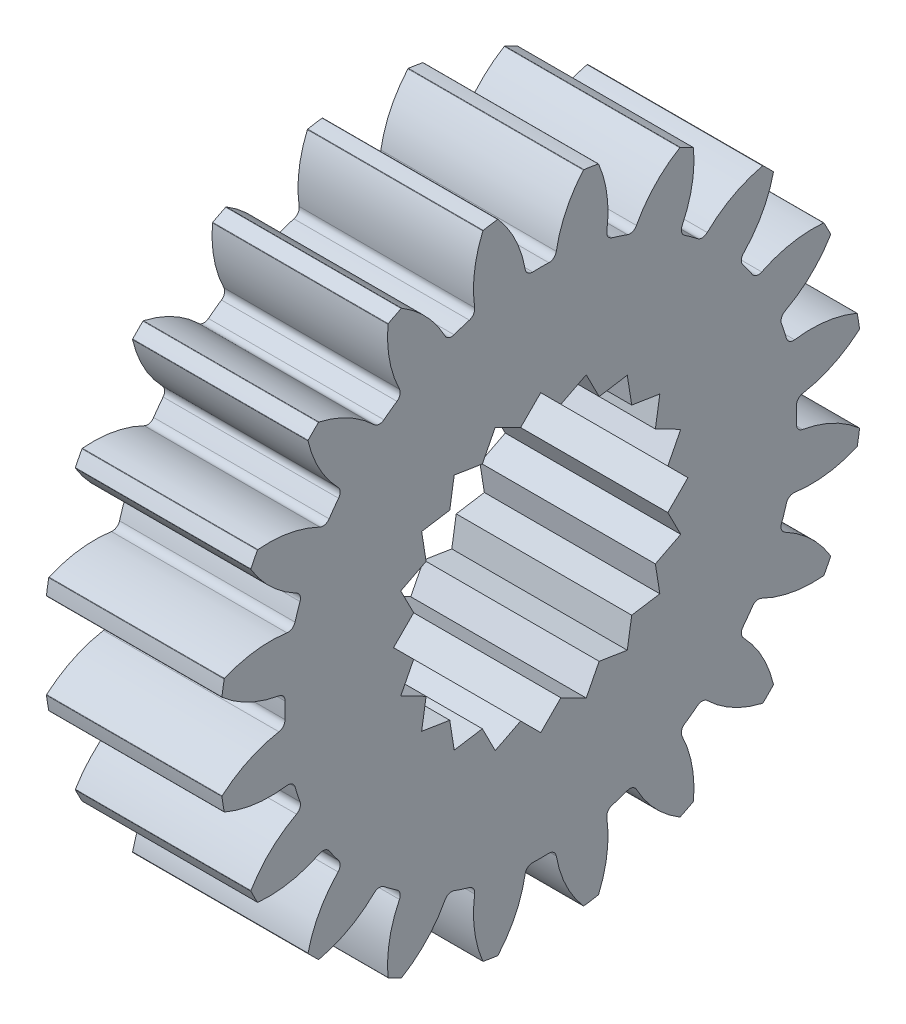
SolidWorks part; units mm, degrees
ref_plane "Plane1" through (0, 0, 0) normal (0, 0, 1) x (1, 0, 0)
ref_plane "Plane2" through (0, 0, 0) normal (0, 1, 0) x (1, 0, 0)
ref_plane "Plane3" through (0, 0, 0) normal (1, 0, 0) x (0, 0, -1)
sketch "HoldingSke" plane through (0, 0, 0) normal (0, 1, 0) x (1, 0, 0)
  line L0 (0, 0) -> (1.8794, -0.684)
  line L1 (-15, 0) -> (100, 0) construction
  line L2 (0, 0) -> (-2.1039, 2.3779)
  line L3 (0, 0) -> (-11.863, 4.5341)
  line L4 (0, 0) -> (8.1152, 2.9537)
  line L5 (0, 0) -> (-46.8476, -17.4728)
  line L6 (0, 0) -> (-2.4869, -1.6779)
  line L7 (-2.1039, 2.3779) -> (8.6586, 51.2059)
  line L8 (-76.2, 54.61) -> (-75.9, 54.61)
  line L9 (-71.009, 38.7566) -> (-53.1078, 45.2721)
  line L10 (-76.2, 71.12) -> (104.1128, 71.12)
  line L11 (0, 0) -> (-3, 0)
  line L12 (-76.2, 101.6) -> (-76.181, 101.6)
  line L13 (24.9733, 27.94) -> (52.9518, 28.4284)
  line L14 (24.9733, 27.94) -> (24.9743, 27.94)
  line L15 (24.9733, 27.94) -> (100.4006, 29.5858)
  line L16 (-63.627, -0.5) -> (-12.827, -0.5)
  circle A0 centre (0, 0) radius 1
  circle A1 centre (0, 0) radius 4.374
  circle A2 centre (0, 0) radius 37.5
  circle A3 centre (0, 0) radius 1
  dimension "MHD" = 8.748
  dimension "Hub_dia" = 75
  dimension "Bore" = 2
  dimension "MBD" = 2
  dimension "Num_teeth" = 20
  dimension "Pitch" = 2
  dimension "Overall_len" = 50
  dimension "Show_teeth" = 20
  dimension "Thickness" = 3
  dimension "OAL" = 50.0001
  dimension "T_dim" = 0.3
  dimension "Ap" = 20
  dimension "H" = 19.05
  dimension "Pitch_radius" = 180.3128
  dimension "Width" = 3
  dimension "Backlash" = 0.019
  dimension "Addendum_fac" = 1
  dimension "Dedendum_fac" = 1.25
  dimension "Clearance_fac" = 0.25
  dimension "Dedendum_add" = 0.001
  dimension "Module" = 0.5
sketch "BasProSke" plane through (0, 0, 0) normal (0, 1, 0) x (1, 0, 0)
  line L0 (-10, 0) -> (60, 0) construction
  line L1 (0, 0) -> (0, 5.5)
  line L2 (0, 0) -> (3, 0)
  line L3 (3, 0) -> (3, 5.5)
  line L4 (3, 5.5) -> (0, 5.5)
  dimension "Thickness" = 3
  dimension "Diameter" = 11
revolve "Base-Revolve" add sketch "BasProSke" angle 360 about L0
sketch "TooCutSke" plane through (0, 0, 0) normal (1, 0, 0) x (0, 0, -1)
  line L1 (0, 0) -> (0, 107) construction
  line L2 (0, 0) -> (-0.4255, 4.9819) construction
  line L3 (0, 0) -> (-1.5603, 9.8514) construction
  line L4 (-0.4255, 4.9819) -> (-0.7802, 4.9257) construction
  arc A0 (0.2499, 4.3669) -> (-0.2499, 4.3669) centre (0, 0) ccw
  arc A1 (0.7528, 5.4739) -> (-0.7528, 5.4739) centre (0, 0) ccw
  circle A2 centre (0, 0) radius 5 construction
  circle A3 centre (0, 0) radius 4.6985 construction
  arc A4 (-0.2499, 4.3669) -> (-0.7528, 5.4739) centre (-2.2361, 4.1322) ccw
  arc A5 (0.7528, 5.4739) -> (0.2499, 4.3669) centre (2.2361, 4.1322) ccw
  dimension "Root_dia" = 8.748
  dimension "Overcut_dia" = 11.0508
  dimension "Pitch_dia" = 10
  dimension "Base_dia" = 9.3969
  dimension "Flank_rad" = 2
  dimension "Half_ang" = 9
  dimension "Half_CT" = 0.359
extrude "ToothCut" cut sketch "TooCutSke" along normal through all
fillet "Breaks" radius 0.01 2 edges at (1.5, 5.451, -0.7325) (1.5, 5.451, 0.7325) tangent propagation no
fillet "RootFillets" radius 0.126 2 edges at (1.5, 4.3669, -0.2499) (1.5, 4.3669, 0.2499)
pattern_circular "TeethCuts" count 20 every 18 about axis through (-10, 0, 0) along (1, 0, 0) of "ToothCut", "RootFillets", "Breaks"
sketch "HubNeaOneSke" plane through (0, 0, 0) normal (-1, 0, 0) x (0, 0, 1)
  circle A0 centre (0, 0) radius 4.374
  dimension "Diameter" = 8.748
extrude "HubNearOne" [suppressed] add sketch "HubNeaOneSke" along normal blind 47.0001
sketch "HubNeaBotSke" plane through (0, 0, 0) normal (-1, 0, 0) x (0, 0, 1)
  circle A0 centre (0, 0) radius 4.374
  dimension "Diameter" = 8.748
extrude "HubNearBoth" [suppressed] add sketch "HubNeaBotSke" along normal blind 23.5
ref_plane "FarPln" through (3, 0, 0) normal (1, 0, 0) x (0, 0, -1)
sketch "HubFarSke" plane through (3, 0, 0) normal (1, 0, 0) x (0, 0, -1)
  circle A0 centre (0, 0) radius 4.374
  dimension "Diameter" = 8.748
extrude "HubFar" [suppressed] add sketch "HubFarSke" along normal blind 23.5
sketch "BorSke" plane through (0, 0, 0) normal (1, 0, 0) x (0, 0, -1)
  circle A0 centre (0, 0) radius 1
  dimension "Diameter" = 2
extrude "Bore" cut sketch "BorSke" along normal mid plane 100.0001
sketch "KeySke" plane through (0, 0, 0) normal (1, 0, 0) x (0, 0, -1)
  line L0 (-0.4, 0) -> (-0.4, 1.3)
  line L1 (-0.4, 1.3) -> (0.4, 1.3)
  line L2 (0.4, 1.3) -> (0.4, 0)
  line L3 (0, 0) -> (0, 34) construction
  line L4 (-0.4, 0) -> (0.4, 0)
  dimension "Offset" = 1.3
  dimension "Width" = 0.8
extrude "Keyway" [suppressed] cut sketch "KeySke" along normal mid plane 100.0001
pattern_circular "Keyway2" [suppressed] count 2 every 90 about axis through (-10, 0, 0) along (1, 0, 0)
sketch "Sketch1" plane through (0, 0, 0) normal (-1, 0, 0) x (0, 0, 1)
  line L0 (0, 2.0758) -> (0, 2.375) construction
  line L1 (-0.3247, 2.0503) -> (0, 2.375)
  line L2 (0, 2.375) -> (0.3247, 2.0503)
  line L3 (0.7339, 2.2588) -> (0.9424, 1.8496)
  line L4 (0.3247, 2.0503) -> (0.7339, 2.2588)
  line L5 (1.396, 1.9214) -> (1.4678, 1.4678)
  line L6 (0.9424, 1.8496) -> (1.396, 1.9214)
  line L7 (1.9214, 1.396) -> (1.8496, 0.9424)
  line L8 (1.4678, 1.4678) -> (1.9214, 1.396)
  line L9 (2.2588, 0.7339) -> (2.0503, 0.3247)
  line L10 (1.8496, 0.9424) -> (2.2588, 0.7339)
  line L11 (2.375, 0) -> (2.0503, -0.3247)
  line L12 (2.0503, 0.3247) -> (2.375, 0)
  line L13 (2.2588, -0.7339) -> (1.8496, -0.9424)
  line L14 (2.0503, -0.3247) -> (2.2588, -0.7339)
  line L15 (1.9214, -1.396) -> (1.4678, -1.4678)
  line L16 (1.8496, -0.9424) -> (1.9214, -1.396)
  line L17 (1.396, -1.9214) -> (0.9424, -1.8496)
  line L18 (1.4678, -1.4678) -> (1.396, -1.9214)
  line L19 (0.7339, -2.2588) -> (0.3247, -2.0503)
  line L20 (0.9424, -1.8496) -> (0.7339, -2.2588)
  line L21 (0, -2.375) -> (-0.3247, -2.0503)
  line L22 (0.3247, -2.0503) -> (0, -2.375)
  line L23 (-0.7339, -2.2588) -> (-0.9424, -1.8496)
  line L24 (-0.3247, -2.0503) -> (-0.7339, -2.2588)
  line L25 (-1.396, -1.9214) -> (-1.4678, -1.4678)
  line L26 (-0.9424, -1.8496) -> (-1.396, -1.9214)
  line L27 (-1.9214, -1.396) -> (-1.8496, -0.9424)
  line L28 (-1.4678, -1.4678) -> (-1.9214, -1.396)
  line L29 (-2.2588, -0.7339) -> (-2.0503, -0.3247)
  line L30 (-1.8496, -0.9424) -> (-2.2588, -0.7339)
  line L31 (-2.375, 0) -> (-2.0503, 0.3247)
  line L32 (-2.0503, -0.3247) -> (-2.375, 0)
  line L33 (-2.2588, 0.7339) -> (-1.8496, 0.9424)
  line L34 (-2.0503, 0.3247) -> (-2.2588, 0.7339)
  line L35 (-1.9214, 1.396) -> (-1.4678, 1.4678)
  line L36 (-1.8496, 0.9424) -> (-1.9214, 1.396)
  line L37 (-1.396, 1.9214) -> (-0.9424, 1.8496)
  line L38 (-1.4678, 1.4678) -> (-1.396, 1.9214)
  line L39 (-0.7339, 2.2588) -> (-0.3247, 2.0503)
  line L40 (-0.9424, 1.8496) -> (-0.7339, 2.2588)
  circle A0 centre (0, 0) radius 2.375 construction
  circle A1 centre (0, 0) radius 2.0758 construction
  point P68 (0, 0)
  dimension "D4" = 4.75
  dimension "D1" = 45
  dimension "D2" = 45
  dimension "D3" = 20
extrude "Cut-Extrude1" cut sketch "Sketch1" against normal blind 10
sketch "Sketch2" plane through (0, 0, 0) normal (-1, 0, 0) x (0, 0, 1)
  line L6 (8.1761, -2.2811) -> (4.6692, -9.1639)
  line L7 (4.6692, -9.1639) -> (-2.9603, -7.9555)
  line L8 (8.1761, -2.2811) -> (4.6692, -9.1639)
  line L9 (4.6692, -9.1639) -> (-2.9603, -7.9555)
  line L1134 (-2.0358, 1.4791) -> (-1.9597, 0.9985)
  line L1135 (-1.9597, 0.9985) -> (-2.3933, 0.7776)
  line L1136 (-2.3933, 0.7776) -> (-2.1724, 0.3441)
  line L1137 (-2.1724, 0.3441) -> (-2.5164, 0)
  line L1138 (-2.5164, 0) -> (-2.1724, -0.3441)
  line L1139 (-2.1724, -0.3441) -> (-2.3933, -0.7776)
  line L1140 (-2.3933, -0.7776) -> (-1.9597, -0.9985)
  line L1141 (-1.9597, -0.9985) -> (-2.0358, -1.4791)
  line L1142 (-2.0358, -1.4791) -> (-1.5552, -1.5552)
  line L1143 (-1.5552, -1.5552) -> (-1.4791, -2.0358)
  line L1144 (-1.4791, -2.0358) -> (-0.9985, -1.9597)
  line L1145 (-0.9985, -1.9597) -> (-0.7776, -2.3933)
  line L1146 (-0.7776, -2.3933) -> (-0.3441, -2.1724)
  line L1147 (-0.3441, -2.1724) -> (0, -2.5164)
  line L1148 (0, -2.5164) -> (0.3441, -2.1724)
  line L1149 (0.3441, -2.1724) -> (0.7776, -2.3933)
  line L1150 (0.7776, -2.3933) -> (0.9985, -1.9597)
  line L1151 (0.9985, -1.9597) -> (1.4791, -2.0358)
  line L1152 (1.4791, -2.0358) -> (1.5552, -1.5552)
  line L1153 (2.0358, -1.4791) -> (1.9597, -0.9985)
  line L1154 (1.9597, -0.9985) -> (2.3933, -0.7776)
  line L1155 (1.5552, -1.5552) -> (2.0358, -1.4791)
  line L1156 (2.3933, -0.7776) -> (2.1724, -0.3441)
  line L1157 (2.1724, -0.3441) -> (2.5164, 0)
  line L1158 (2.5164, 0) -> (2.1724, 0.3441)
  line L1159 (2.1724, 0.3441) -> (2.3933, 0.7776)
  line L1160 (2.3933, 0.7776) -> (1.9597, 0.9985)
  line L1161 (1.9597, 0.9985) -> (2.0358, 1.4791)
  line L1162 (2.0358, 1.4791) -> (1.5552, 1.5552)
  line L1163 (1.5552, 1.5552) -> (1.4791, 2.0358)
  line L1164 (1.4791, 2.0358) -> (0.9985, 1.9597)
  line L1165 (0.9985, 1.9597) -> (0.7776, 2.3933)
  line L1166 (0.7776, 2.3933) -> (0.3441, 2.1724)
  line L1167 (0.3441, 2.1724) -> (0, 2.5164)
  line L1168 (0, 2.5164) -> (-0.3441, 2.1724)
  line L1169 (-0.3441, 2.1724) -> (-0.7776, 2.3933)
  line L1170 (-0.7776, 2.3933) -> (-0.9985, 1.9597)
  line L1171 (-0.9985, 1.9597) -> (-1.4791, 2.0358)
  line L1172 (-1.4791, 2.0358) -> (-1.5552, 1.5552)
  line L1173 (-1.5552, 1.5552) -> (-2.0358, 1.4791)
  line L1174 (-2.0358, 1.4791) -> (-1.9597, 0.9985)
  line L1175 (-1.9597, 0.9985) -> (-2.3933, 0.7776)
  line L1176 (-2.3933, 0.7776) -> (-2.1724, 0.3441)
  line L1177 (-2.1724, 0.3441) -> (-2.5164, 0)
  line L1178 (-2.5164, 0) -> (-2.1724, -0.3441)
  line L1179 (-2.1724, -0.3441) -> (-2.3933, -0.7776)
  line L1180 (-2.3933, -0.7776) -> (-1.9597, -0.9985)
  line L1181 (-1.9597, -0.9985) -> (-2.0358, -1.4791)
  line L1182 (-2.0358, -1.4791) -> (-1.5552, -1.5552)
  line L1183 (-1.5552, -1.5552) -> (-1.4791, -2.0358)
  line L1184 (-1.4791, -2.0358) -> (-0.9985, -1.9597)
  line L1185 (-0.9985, -1.9597) -> (-0.7776, -2.3933)
  line L1186 (-0.7776, -2.3933) -> (-0.3441, -2.1724)
  line L1187 (-0.3441, -2.1724) -> (0, -2.5164)
  line L1188 (0, -2.5164) -> (0.3441, -2.1724)
  line L1189 (0.3441, -2.1724) -> (0.7776, -2.3933)
  line L1190 (0.7776, -2.3933) -> (0.9985, -1.9597)
  line L1191 (0.9985, -1.9597) -> (1.4791, -2.0358)
  line L1192 (1.4791, -2.0358) -> (1.5552, -1.5552)
  line L1193 (2.0358, -1.4791) -> (1.9597, -0.9985)
  line L1194 (1.9597, -0.9985) -> (2.3933, -0.7776)
  line L1195 (1.5552, -1.5552) -> (2.0358, -1.4791)
  line L1196 (2.3933, -0.7776) -> (2.1724, -0.3441)
  line L1197 (2.1724, -0.3441) -> (2.5164, 0)
  line L1198 (2.5164, 0) -> (2.1724, 0.3441)
  line L1199 (2.1724, 0.3441) -> (2.3933, 0.7776)
  line L1200 (2.3933, 0.7776) -> (1.9597, 0.9985)
  line L1201 (1.9597, 0.9985) -> (2.0358, 1.4791)
  line L1202 (2.0358, 1.4791) -> (1.5552, 1.5552)
  line L1203 (1.5552, 1.5552) -> (1.4791, 2.0358)
  line L1204 (1.4791, 2.0358) -> (0.9985, 1.9597)
  line L1205 (0.9985, 1.9597) -> (0.7776, 2.3933)
  line L1206 (0.7776, 2.3933) -> (0.3441, 2.1724)
  line L1207 (0.3441, 2.1724) -> (0, 2.5164)
  line L1208 (0, 2.5164) -> (-0.3441, 2.1724)
  line L1209 (-0.3441, 2.1724) -> (-0.7776, 2.3933)
  line L1210 (-0.7776, 2.3933) -> (-0.9985, 1.9597)
  line L1211 (-0.9985, 1.9597) -> (-1.4791, 2.0358)
  line L1212 (-1.4791, 2.0358) -> (-1.5552, 1.5552)
  line L1213 (-1.5552, 1.5552) -> (-2.0358, 1.4791)
  dimension "D1" = 10
  dimension "D2" = 0.1
extrude "Cut-Extrude2" cut sketch "Sketch2" against normal up to next contours L1174 L1175 L1176 L1177 L1178 L1179 L1180 L1181 L1182 L1183 L1184 L1185 L1186 L1187 L1188 L1189 L1190 L1191 L1192 L1195 L1193 L1194 L1196 L1197 L1198 L1199 L1200 L1201 L1202 L1203 L1204 L1205 L1206 L1207 L1208 L1209 L1210 L1211 L1212 L1213
equation "' \"Module@HoldingSke\" = 6.35"
equation "' \"Num_teeth@HoldingSke\" = 12"
equation "' \"Ap@HoldingSke\" =  20"
equation "' \"Ap@HoldingSke\" = 20"
equation "' \"Width@HoldingSke\" = 0.5 * 25.4"
equation "' \"Hub_dia@HoldingSke\"= 1 * 25.4"
equation "' \"Hub_dia@HoldingSke\" = 1 * 25.4"
equation "' \"Overall_len@HoldingSke\" = 1.0 * 25.4"
equation "' \"Bore@HoldingSke\" = 0.75 * 25.4"
equation "' \"T_dim@HoldingSke\" = 0.1 * 25.4"
equation "' \"Width@KeySke\" = 0.25 * 25.4"
equation "' \"Show_teeth@HoldingSke\" = 13"
equation "' \"Backlash@HoldingSke\" = 0.009 * 25.4"
equation "' \"Addendum_fac@HoldingSke\" = 1.0"
equation "' \"Dedendum_fac@HoldingSke\" = 1.25"
equation "' \"Dedendum_add@HoldingSke\" = 0.00005 * 25.4"
equation "' \"Clearance_fac@HoldingSke\" = 0.25"
equation "\"Pitch@HoldingSke\" = 1 / \"Module@HoldingSke\""
equation "\"Overcut_dia@TooCutSke\" = (\"Num_teeth@HoldingSke\" + 2 * \"Addendum_fac@HoldingSke\") / \"Pitch@HoldingSke\" + 0.002 * 25.4"
equation "\"Pitch_dia@TooCutSke\" = \"Num_teeth@HoldingSke\" / \"Pitch@HoldingSke\""
equation "\"Base_dia@TooCutSke\" = \"Num_teeth@HoldingSke\" / \"Pitch@HoldingSke\" * cos((\"Ap@HoldingSke\"  * 3.14159265 / 180))"
equation "\"Root_dia@TooCutSke\" = (\"Num_teeth@HoldingSke\" + 2) / \"Pitch@HoldingSke\" - 2 * (\"Addendum_fac@HoldingSke\" + \"Dedendum_fac@HoldingSke\") / \"Pitch@HoldingSke\" - \"Dedendum_add@HoldingSke\" * 2"
equation "\"Half_ang@TooCutSke\" = 180 / \"Num_teeth@HoldingSke\""
equation "\"Half_CT@TooCutSke\" = \"Num_teeth@HoldingSke\" / \"Pitch@HoldingSke\" * sin((3.14159265 / 2 / \"Num_teeth@HoldingSke\")) / 2 - 7 * \"Backlash@HoldingSke\" / 4"
equation "\"Flank_rad@TooCutSke\" = \"Num_teeth@HoldingSke\" / \"Pitch@HoldingSke\" / 5"
equation "\"Radius@RootFillets\" = \"Clearance_fac@HoldingSke\" / \"Pitch@HoldingSke\" + \"Dedendum_add@HoldingSke\""
equation "\"Break_rad@Breaks\" = 0.02 / \"Pitch@HoldingSke\""
equation "\"Thickness@HoldingSke\" = \"Width@HoldingSke\""
equation "\"OAL@HoldingSke\" = \"Thickness@HoldingSke\""
equation "\"MHD@HoldingSke\" = (\"Num_teeth@HoldingSke\" + 2) / \"Pitch@HoldingSke\" - 2 * (\"Addendum_fac@HoldingSke\" + \"Dedendum_fac@HoldingSke\")  / \"Pitch@HoldingSke\" - \"Dedendum_add@HoldingSke\" * 2"
equation "\"MBD@HoldingSke\" = (\"Num_teeth@HoldingSke\" + 2) / \"Pitch@HoldingSke\" - 2 * (\"Addendum_fac@HoldingSke\" + \"Dedendum_fac@HoldingSke\")  / \"Pitch@HoldingSke\" - \"Dedendum_add@HoldingSke\" * 2 - 0.002 * 25.4"
equation "\"MHD@HoldingSke\" = ((sgn( \"MHD@HoldingSke\" - \"Hub_dia@HoldingSke\" )-1)*( \"MHD@HoldingSke\" - \"Hub_dia@HoldingSke\" ))/-2+ \"Hub_dia@HoldingSke\""
equation "\"MBD@HoldingSke\" = ((sgn( \"MBD@HoldingSke\" - \"Bore@HoldingSke\" )-1)*( \"MBD@HoldingSke\" - \"Bore@HoldingSke\" ))/-2+ \"Bore@HoldingSke\""
equation "\"OAL@HoldingSke\" = ((sgn( \"OAL@HoldingSke\" - \"Overall_len@HoldingSke\" )+1)*( \"OAL@HoldingSke\" - \"Overall_len@HoldingSke\" ))/2 + \"Overall_len@HoldingSke\" + 0.000002 * 25.4"
equation "\"Num_teeth@TeethCuts\" = int( \"Show_teeth@HoldingSke\" ) + 1"
equation "\"Num_teeth@TeethCuts\" = ((sgn( \"Num_teeth@TeethCuts\" - \"Num_teeth@HoldingSke\" )-1)*( \"Num_teeth@TeethCuts\" - \"Num_teeth@HoldingSke\" ))/-2+ \"Num_teeth@HoldingSke\""
equation "\"Num_teeth@TeethCuts\" = ((sgn( \"Num_teeth@TeethCuts\" - 2.0)+1)*( \"Num_teeth@TeethCuts\" - 2.0))/2 +2.0"
equation "\"Angle@TeethCuts\" = 360.0 / \"Num_teeth@HoldingSke\""
equation "\"Diameter@BasProSke\" = (\"Num_teeth@HoldingSke\" + 2 * \"Addendum_fac@HoldingSke\") / \"Pitch@HoldingSke\""
equation "\"Thickness@BasProSke\"  = \"Thickness@HoldingSke\""
equation "' \"Fillet_rad@BasProSke\" =  \"Thickness@HoldingSke\" * 0.05"
equation "' \"Fillet_rad@BasProSke\" = \"Thickness@HoldingSke\" * 0.05"
equation "\"MHD@HoldingSke\" = ((sgn( \"MHD@HoldingSke\" - \"Root_dia@TooCutSke\" )-1)*( \"MHD@HoldingSke\" - \"Root_dia@TooCutSke\" ))/-2+ \"Root_dia@TooCutSke\""
equation "\"Diameter@HubNeaOneSke\" = \"MHD@HoldingSke\""
equation "\"Length@HubNearOne\" = \"OAL@HoldingSke\" - \"Thickness@BasProSke\""
equation "\"Diameter@HubNeaBotSke\" = \"MHD@HoldingSke\""
equation "\"Length@HubNearBoth\" = ( \"OAL@HoldingSke\" - \"Thickness@BasProSke\" ) / 2.0"
equation "\"Thickness@FarPln\" = \"Thickness@BasProSke\""
equation "\"Diameter@HubFarSke\" = \"MHD@HoldingSke\""
equation "\"Length@HubFar\" = ( \"OAL@HoldingSke\" - \"Thickness@BasProSke\" ) / 2.0"
equation "\"Diameter@BorSke\" = \"MBD@HoldingSke\""
equation "\"D1@Bore\" = \"OAL@HoldingSke\" * 2.0"
equation "\"D1@Keyway\" = \"OAL@HoldingSke\" * 2.0"
equation "\"Offset@KeySke\" = \"T_dim@HoldingSke\" + \"MBD@HoldingSke\" / 2.0"
